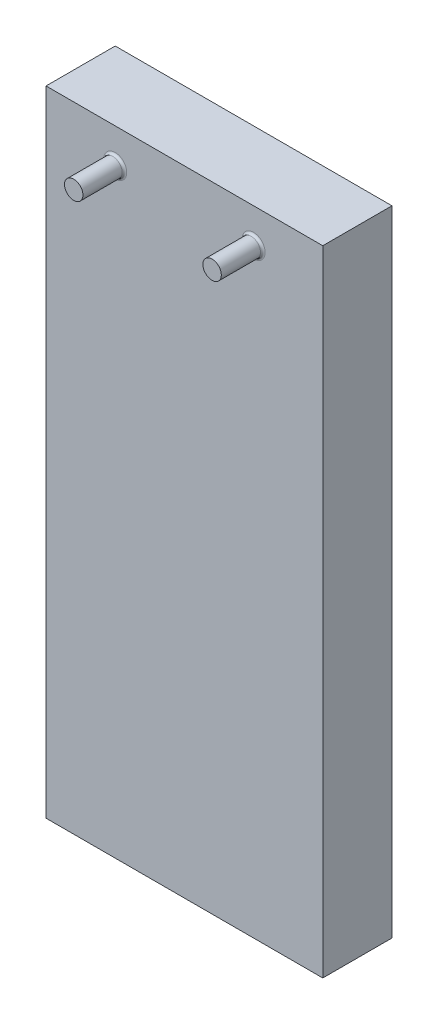
SolidWorks part; units mm, degrees
ref_plane "Front Plane" through (0, 0, 0) normal (0, 0, 1) x (1, 0, 0)
ref_plane "Top Plane" through (0, 0, 0) normal (0, 1, 0) x (1, 0, 0)
ref_plane "Right Plane" through (0, 0, 0) normal (1, 0, 0) x (0, 0, -1)
sketch "Sketch1" plane through (0, 0, 0) normal (0, 1, 0) x (1, 0, 0)
  line L1 (-60, -15) -> (60, -15)
  line L2 (-60, -15) -> (-60, 15)
  line L3 (-60, 15) -> (60, 15)
  line L4 (60, -15) -> (60, 15)
  line L5 (-60, -15) -> (60, 15) construction
  line L6 (-60, 15) -> (60, -15) construction
  point P0 (0, 0)
  dimension "D1" = 120
  dimension "D2" = 30
extrude "Boss-Extrude1" add sketch "Sketch1" along normal blind 275
sketch "Sketch2" plane through (0, 0, 15) normal (0, 0, 1) x (1, 0, 0)
  line L0 (-60, 245) -> (60, 245)
  line L1 (-60, 275) -> (-60, 0) construction
  line L2 (60, 275) -> (60, 0) construction
  line L3 (-60, 275) -> (60, 275) construction
  line L4 (-60, 245) -> (-60, 275)
  line L5 (-60, 260) -> (60, 260) construction
  circle A2 centre (-30, 260) radius 4
  circle A3 centre (30, 260) radius 4
  dimension "D4" = 8
  dimension "D1" = 30
  dimension "D2" = 30
  dimension "D3" = 30
extrude "Boss-Extrude2" add sketch "Sketch2" along normal blind 18 contours L5 A3 | A3 L5 | L5 A2 | A2 L5 region at (-30, 261.6977, 15) region at (30, 261.6977, 15) region at (30, 258.3023, 15) region at (-30, 258.3023, 15)
fillet "Fillet1" radius 1 2 edges at (26, 260, 15) (-34, 260, 15)
equation "\"PCWidth\"= 340mm'Distance of longest part parallel to GPU(ussually GPU)"
equation "\"PCLength\"= 145mm'Length across I/O from PS to GPU"
equation "\"PCHeight\"= 180mm'Tallest point with mobo laying flat"
equation "\"WallThickness\"= 9mm'Thickness of each outer tank wall"
equation "\"ThermoBarrierThickness\"= 6mm'Thickness of barrier between hot side and cold side"
equation "\"HotSideGap\"= 36mm'Space in the hot side for a pump"
equation "\"PCClearance\"= 30mm'Clearance from top of tank to top of PC"
equation "\"RadiatorHeight\"= 275mm'Final Height from ground of radiators"
equation "\"D1@Boss-Extrude1\"=\"RadiatorHeight\""
